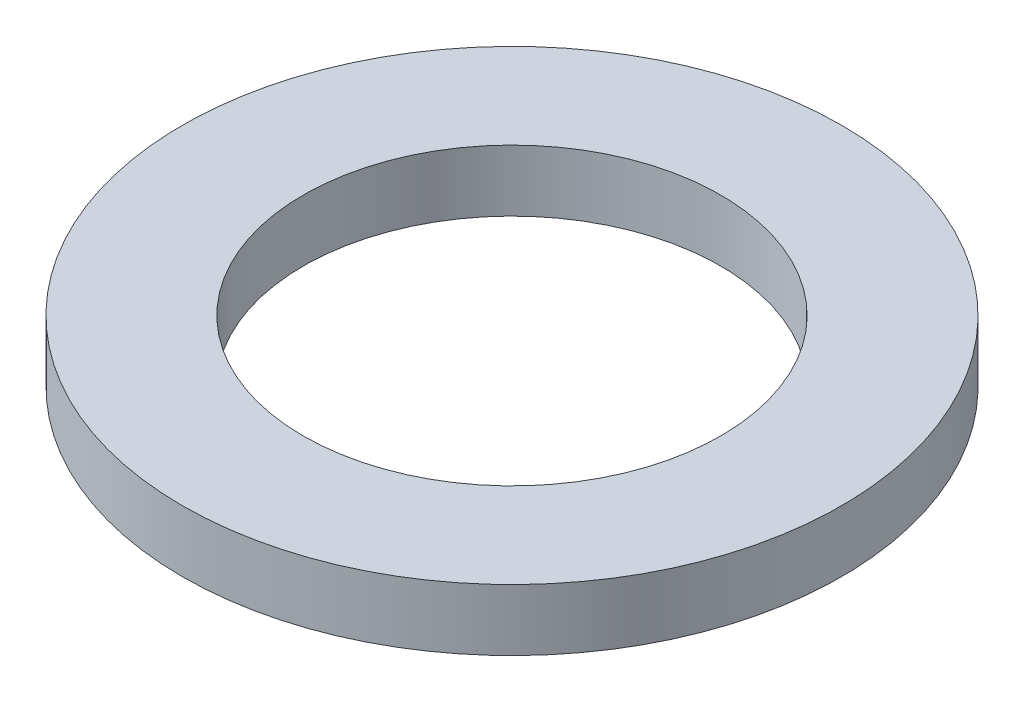
SolidWorks part; units mm, degrees
ref_plane "Front Plane" through (0, 0, 0) normal (0, 0, 1) x (1, 0, 0)
ref_plane "Top Plane" through (0, 0, 0) normal (0, 1, 0) x (1, 0, 0)
ref_plane "Right Plane" through (0, 0, 0) normal (1, 0, 0) x (0, 0, -1)
sketch "Sketch1" plane through (0, 0, 0) normal (0, 1, 0) x (1, 0, 0)
  circle A0 centre (0, 0) radius 75
  dimension "FLANGE_OD" = 150
extrude "Boss-Extrude1" add sketch "Sketch1" along normal blind 14
sketch "Sketch2" plane through (0, 0, 0) normal (0, 1, 0) x (1, 0, 0)
  circle A0 centre (0, 0) radius 47.5
  dimension "BORE_D" = 95
extrude "Cut-Extrude1" cut sketch "Sketch2" along normal through all
sketch "Sketch3" plane through (0, 14, 0) normal (0, 1, 0) x (1, 0, 0)
  circle A0 centre (0, 0) radius 29.3215 construction
  circle A1 centre (-29.3215, 0) radius 1.8237
  dimension "BOLT_D" = 3.6473
  dimension "BOLT_PCD" = 58.6429
extrude "Cut-Extrude2" cut sketch "Sketch3" against normal blind 12.7455 rebuild error yes
pattern_circular "CirPattern1" count 4 over 360 rebuild error yes
